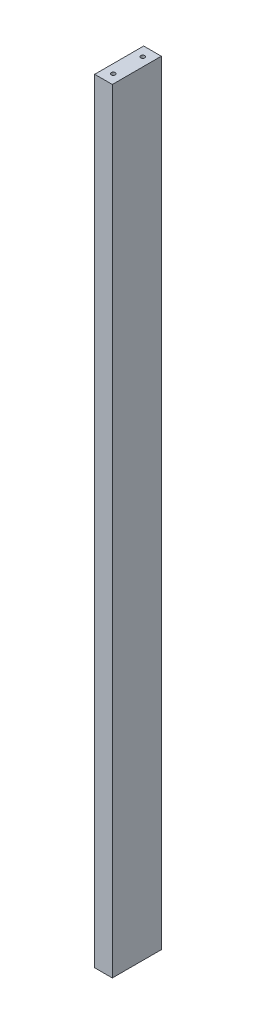
SolidWorks part; units mm, degrees
material "Beech"
ref_plane "Front Plane" through (0, 0, 0) normal (0, 0, 1) x (1, 0, 0)
ref_plane "Top Plane" through (0, 0, 0) normal (0, 1, 0) x (1, 0, 0)
ref_plane "Right Plane" through (0, 0, 0) normal (1, 0, 0) x (0, 0, -1)
sketch "Sketch1" plane through (0, 0, 0) normal (0, 1, 0) x (1, 0, 0)
  line L1 (0, 0) -> (18, 0)
  line L2 (0, 0) -> (0, 50)
  line L3 (0, 50) -> (18, 50)
  line L4 (18, 0) -> (18, 50)
  dimension "D1" = 18
  dimension "D2" = 50
extrude "base" add sketch "Sketch1" along normal blind 789.8
hole_wizard "end bolt holes for inserts" positions "Sketch2" profile "Sketch3" tap size "M5x0.8" standard "ANSI Metric"
sketch "Sketch2" plane through (0, 0, 0) normal (0, -1, 0) x (-1, 0, 0)
  line L1 (-9, 50) -> (-9, 0)
  line L2 (-18, 50) -> (0, 50) construction
  line L3 (0, 0) -> (-18, 0) construction
  line L4 (-9, 10) -> (-18, 25)
  line L5 (-18, 0) -> (-18, 50) construction
  line L6 (-18, 25) -> (-9, 40)
  point P10 (-9, 40)
  point P12 (-9, 10)
  dimension "D1" = 30
sketch "Sketch3" plane through (9, 0, -40) normal (1, 0, 0) x (0, 0, -1)
  line L0 (0, 0) -> (0, 15.2618)
  line L1 (0, 15.2618) -> (2.1, 14)
  line L2 (2.1, 14) -> (2.1, 0)
  line L5 (2.1, 0) -> (0, 0)
  line L10 (0, 15.2618) -> (-2.1, 14) construction
  line L11 (0, -6.35) -> (0, 107.95) construction
  dimension "Tap Drill Dia." = 4.2
  dimension "Tap Drill Depth" = 14
  dimension "Drill Angle" = 118
cosmetic thread "Hole Thread1" parameters "D1"=10, "D2"=5
cosmetic thread "Hole Thread2" parameters "D1"=10, "D2"=5
ref_plane "midplane along length" through (0, 394.9, 0) normal (0, -1, 0) x (-1, 0, 0)
mirror "mirror end bolt holes" about plane through (0, 394.9, 0) normal (0, -1, 0) of "end bolt holes for inserts"
equation "\"board_thickness\" = 18mm"
equation "\"way_width\"= 75mm"
equation "\"way_thickness\"= 50mm"
equation "\"radial_clearance\"= 0.1mm"
equation "\"slider_width\"= \"way_width\"-2* \"radial_clearance\""
equation "\"slider_thickness\" = \"way_thickness\" - 2 * \"radial_clearance\""
equation "\"column_width\"= \"way_width\" + 2 * \"board_thickness\""
equation "\"boxway_slot_width\" = 50mm"
equation "\"keeper_rail_width\" = (\"column_width\" - \"boxway_slot_width\")/2"
equation "\"slider_length\" = 125mm"
equation "\"nut_diameter\"= 22mm"
equation "\"nut_length\"= 15mm"
equation "\"leadscrew_diameter\"= 10mm"
equation "\"leadscrew_radial_clearance\"= 1mm"
equation "\"bearing_bolt_pattern_width\" = 35mm"
equation "\"bearing_bolt_pattern_height\" = 60mm"
equation "\"desktop_bolt_pattern_width\" = 30mm"
equation "\"desktop_bolt_pattern_height\" = 30mm"
equation "\"bearing_bolt_nut_counterbore_diameter\" = 12mm"
equation "\"bearing_bolt_nut_counterbore_depth\"= 10mm"
equation "\"desktop_depth\"= 500mm"
equation "\"desktop_width\"= 650mm"
equation "\"desktop_thickness\"= 15mm"
equation "\"leg_height\"=100mm"
equation "\"leg_width\"=18mm"
equation "\"leg_length\"=500mm"
equation "\"lap_joint_height\" = 50mm"
equation "\"lap_dowel_diameter\"= 8mm"
equation "\"lap_dowel_hole_z_spacing\"=30"
equation "\"D1@Sketch1\"=\"board_thickness\""
equation "\"D2@Sketch1\"=\"lap_joint_height\""
equation "\"D1@Sketch2\"=\"lap_dowel_hole_z_spacing\""
